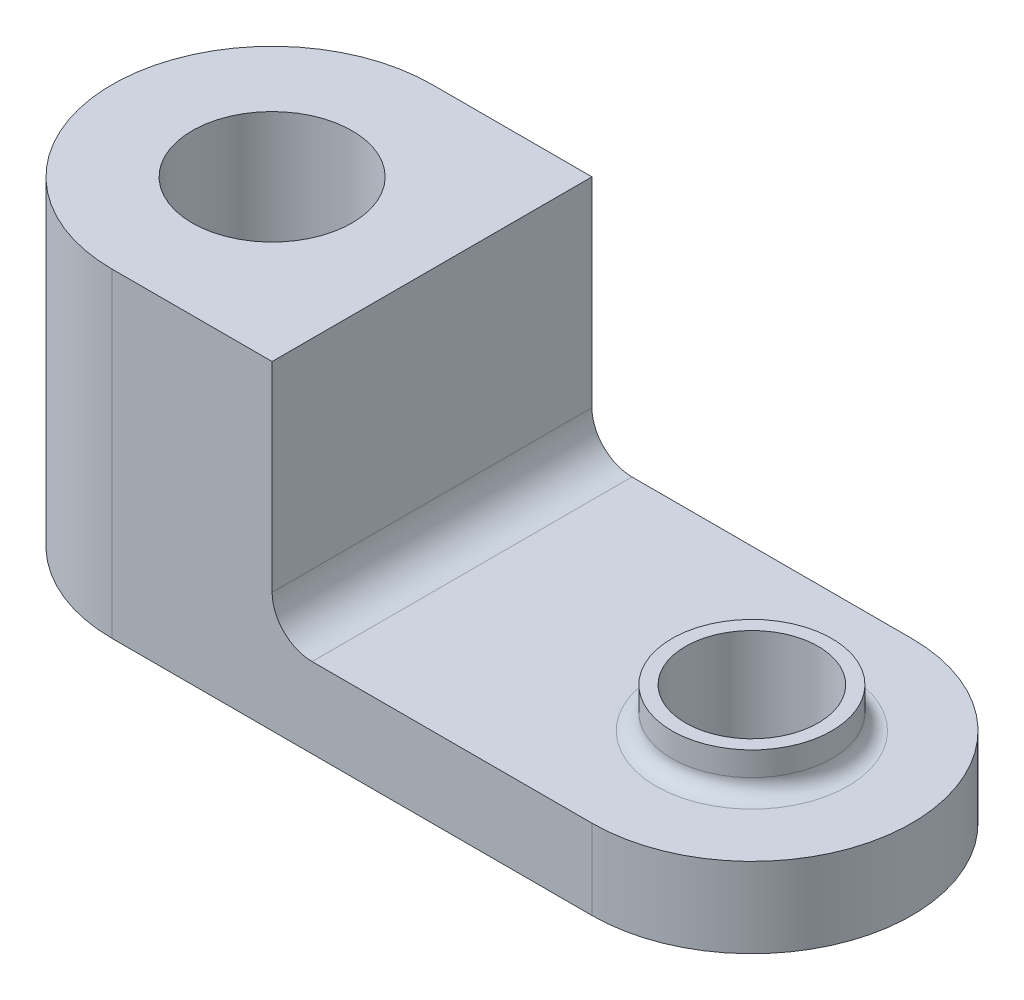
SolidWorks part; units mm, degrees
ref_plane "Front Plane" through (0, 0, 0) normal (0, 0, 1) x (1, 0, 0)
ref_plane "Top Plane" through (0, 0, 0) normal (0, 1, 0) x (1, 0, 0)
ref_plane "Right Plane" through (0, 0, 0) normal (1, 0, 0) x (0, 0, -1)
sketch "Sketch1" plane through (0, 0, 0) normal (0, 1, 0) x (1, 0, 0)
  line L0 (-30, 0) -> (30, 0) construction
  line L1 (-30, 20) -> (30, 20)
  line L2 (-30, -20) -> (30, -20)
  arc A0 (-30, 20) -> (-30, -20) centre (-30, 0) ccw
  arc A1 (30, -20) -> (30, 20) centre (30, 0) ccw
  circle A2 centre (-30, 0) radius 10
  circle A3 centre (30, 0) radius 10
  circle A4 centre (30, 0) radius 8.2994
  point P2 (0, 0)
  dimension "D3" = 20
  dimension "D5" = 20
  dimension "D1" = 0
  dimension "D2" = 20
  dimension "D4" = 60
extrude "Boss-Extrude1" add sketch "Sketch1" along normal blind 10 contours L2 A1 L1 A0 | A2 | A3
sketch "Sketch2" plane through (0, 10, 0) normal (0, 1, 0) x (1, 0, 0)
  line L2 (-10, -20) -> (-30, -20)
  line L3 (-10, 20) -> (-30, 20)
  line L4 (-10, 20) -> (-10, -20)
  arc A0 (-30, 20) -> (-30, -20) centre (-30, 0) ccw
  circle A1 centre (-30, 0) radius 10
  point P9 (0, 0)
  dimension "D3" = 20
  dimension "D1" = 40
  dimension "D2" = 20
extrude "Boss-Extrude2" add sketch "Sketch2" along normal blind 30
extrude "Boss-Extrude3" add sketch "Sketch1<3>" along normal blind 15 contours A3 | A4
sketch "Sketch1<3>" plane through (0, 0, 0) normal (0, 1, 0) x (1, 0, 0) same geometry as "Sketch1"
fillet "Fillet1" radius 2 1 edges at (30, 10, 10)
fillet "Fillet2" radius 5 1 edges at (-10, 10, 0)
